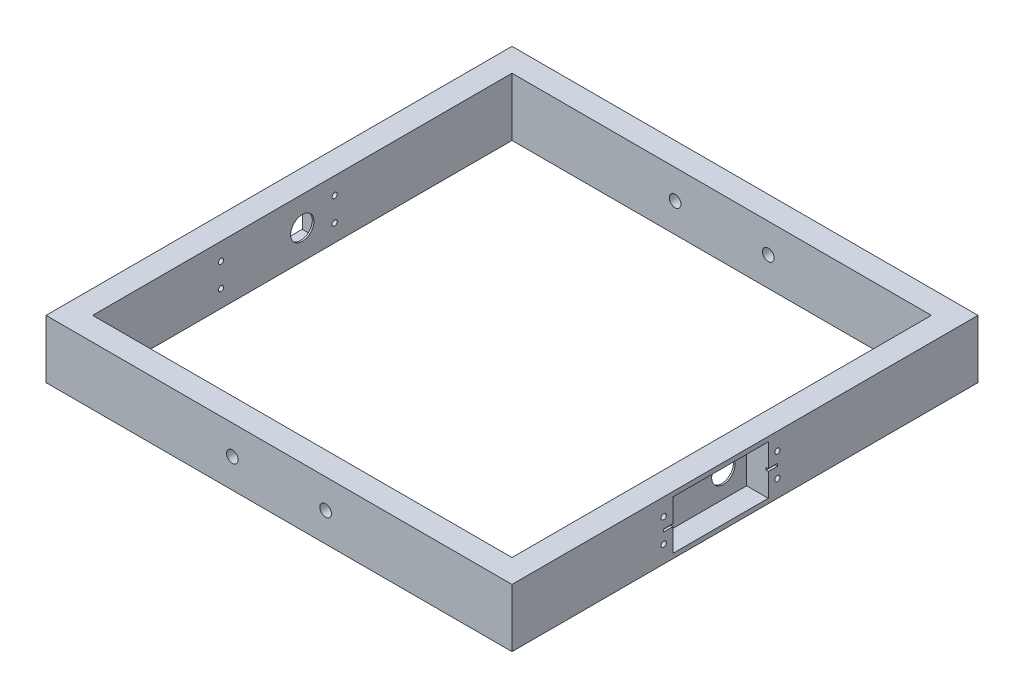
SolidWorks part; units mm, degrees
ref_plane "Front Plane" through (0, 0, 0) normal (0, 0, 1) x (1, 0, 0)
ref_plane "Top Plane" through (0, 0, 0) normal (0, 1, 0) x (1, 0, 0)
ref_plane "Right Plane" through (0, 0, 0) normal (1, 0, 0) x (0, 0, -1)
sketch "Sketch1" plane through (0, 0, 0) normal (0, 1, 0) x (1, 0, 0)
  line L1 (-100, -100) -> (100, -100)
  line L2 (-100, -100) -> (-100, 100)
  line L3 (-100, 100) -> (100, 100)
  line L4 (100, -100) -> (100, 100)
  line L5 (-100, -100) -> (100, 100) construction
  line L6 (-100, 100) -> (100, -100) construction
  point P0 (0, 0)
  dimension "D1" = 200
extrude "Boss-Extrude1" add sketch "Sketch1" along normal blind 25
sketch "Sketch2" plane through (0, 25, 0) normal (0, 1, 0) x (1, 0, 0)
  line L0 (100, 100) -> (-100, 100) construction
  line L1 (-90, -90) -> (90, -90)
  line L2 (-90, -90) -> (-90, 90)
  line L3 (-90, 90) -> (90, 90)
  line L4 (90, -90) -> (90, 90)
  line L5 (-90, -90) -> (90, 90) construction
  line L6 (-90, 90) -> (90, -90) construction
  point P0 (0, 0)
  dimension "D1" = 10
extrude "Cut-Extrude1" cut sketch "Sketch2" against normal blind 25
sketch "Sketch19" plane through (-100, 0, 0) normal (-1, 0, 0) x (0, 0, 1)
  line L0 (-100, 25) -> (-100, 0) construction
  line L1 (-10, 23) -> (31, 23)
  line L2 (-10, 23) -> (-10, 2)
  line L3 (-10, 2) -> (31, 2)
  line L4 (31, 23) -> (31, 2)
  line L5 (-10, 23) -> (31, 2) construction
  line L6 (-10, 2) -> (31, 23) construction
  point P0 (10.5, 12.5)
  point P7 (-100, 12.5)
  point P11 (0, 0)
  dimension "D1" = 41
  dimension "D2" = 21
  dimension "D3" = 90
extrude "Cut-Extrude10" cut sketch "Sketch19" against normal blind 9.3
sketch "Sketch20" plane through (-90.7, 0, 0) normal (-1, 0, 0) x (0, 0, 1)
  line L0 (-10, 23) -> (-10, 2) construction
  circle A0 centre (0, 12.5) radius 5
  point P4 (-10, 12.5)
  dimension "D1" = 10
  dimension "D2" = 10
extrude "Cut-Extrude11" cut sketch "Sketch20" against normal blind 9.3
sketch "Sketch23" plane through (-100, 0, 0) normal (-1, 0, 0) x (0, 0, 1)
  line L0 (-10, 23) -> (-10, 2) construction
  line L1 (35, 11.95) -> (-14, 11.95)
  line L2 (35, 11.95) -> (35, 13.05)
  line L3 (35, 13.05) -> (-14, 13.05)
  line L4 (-14, 11.95) -> (-14, 13.05)
  line L5 (35, 11.95) -> (-14, 13.05) construction
  line L6 (35, 13.05) -> (-14, 11.95) construction
  line L7 (31, 23) -> (-10, 23) construction
  point P0 (10.5, 12.5)
  point P7 (0, 0)
  point P10 (10.5, 23)
  point P11 (-10, 12.5)
  dimension "D1" = 1.1
  dimension "D2" = 4
extrude "Cut-Extrude14" cut sketch "Sketch23" against normal blind 1
ref_plane "Plane5" through (0, 0, 10.5) normal (0, 0, 1) x (1, 0, 0)
ref_plane "Plane6" through (0, 12.5, 0) normal (0, 1, 0) x (1, 0, 0)
sketch "Sketch21" plane through (-100, 0, 0) normal (-1, 0, 0) x (0, 0, 1)
  line L0 (-10, 23) -> (-10, 2) construction
  circle A0 centre (-13.9, 17.6) radius 1.125
  point P4 (-10, 12.5)
  dimension "D3" = 2.25
  dimension "D1" = 3.9
  dimension "D2" = 5.1
extrude "Cut-Extrude12" cut sketch "Sketch21" against normal blind 10
mirror "Mirror1" about plane through (0, 0, 10.5) normal (0, 0, 1) of "Cut-Extrude12" second plane through (0, 12.5, 0) second plane normal (0, 1, 0)
ref_plane "Plane7" through (0, 0, 0) normal (-1, 0, 0) x (0, 0, 1)
mirror "Mirror2" about plane through (0, 0, 0) normal (-1, 0, 0) of "Cut-Extrude14", "Cut-Extrude10", "Cut-Extrude11", "Cut-Extrude12", "Mirror1"
sketch "Sketch22" plane through (0, 0, 100) normal (0, 0, 1) x (1, 0, 0)
  line L0 (-100, 25) -> (-100, 0) construction
  circle A0 centre (-20, 12.5) radius 2.5
  circle A1 centre (20, 12.5) radius 2.5
  point P4 (0, 0)
  point P6 (0, 0)
  point P9 (-100, 12.5)
  dimension "D1" = 5
  dimension "D2" = 40
  dimension "D3" = 20
extrude "Cut-Extrude13" cut sketch "Sketch22" against normal through all
